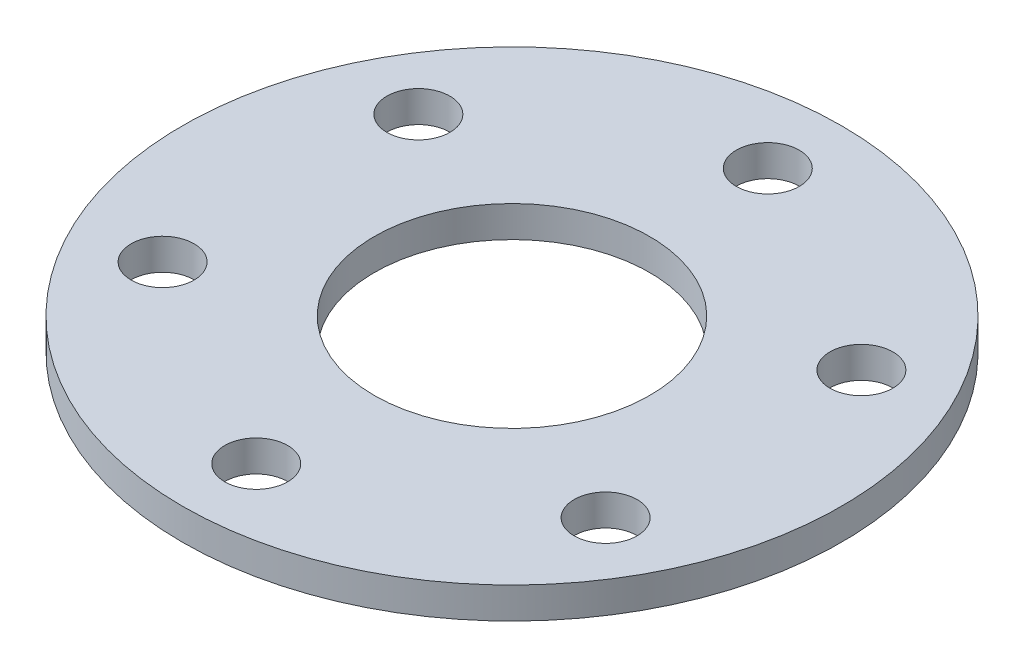
SolidWorks part; units mm, degrees
ref_plane "Front Plane" through (0, 0, 0) normal (0, 0, 1) x (1, 0, 0)
ref_plane "Top Plane" through (0, 0, 0) normal (0, 1, 0) x (1, 0, 0)
ref_plane "Right Plane" through (0, 0, 0) normal (1, 0, 0) x (0, 0, -1)
sketch "Sketch1" plane through (0, 0, 0) normal (0, 1, 0) x (1, 0, 0)
  line L0 (0, 0) -> (0, 26) construction
  circle A0 centre (0, 0) radius 33.5
  circle A1 centre (0, 0) radius 14
  dimension "D1" = 67
  dimension "D3" = 28
  dimension "D2" = 26
extrude "Boss-Extrude1" add sketch "Sketch1" along normal mid plane 3.175
hole_wizard "M6 Clearance Hole1" positions "Sketch2" profile "Sketch3" hole size "M6" standard "ANSI Metric" end condition up to next
sketch "Sketch2" plane through (0, 1.5875, 0) normal (0, 1, 0) x (1, 0, 0)
  point P0 (0, 26)
sketch "Sketch3" plane through (0, 1.5875, -26) normal (1, 0, 0) x (0, 0, 1)
  line L0 (0, 0) -> (0, 3.175)
  line L1 (0, 3.175) -> (3.2, 3.175)
  line L2 (3.2, 3.175) -> (3.2, 0)
  line L5 (3.2, 0) -> (0, 0)
  line L11 (0, -6.35) -> (0, 107.95) construction
  dimension "Thru Hole Dia." = 6.4
  dimension "Thru Hole Depth" = 3.175
pattern_circular "CirPattern1" count 6 over 360 about axis through (0, 1.5875, 0) along (0, -1, 0) of "M6 Clearance Hole1" reverse direction yes
